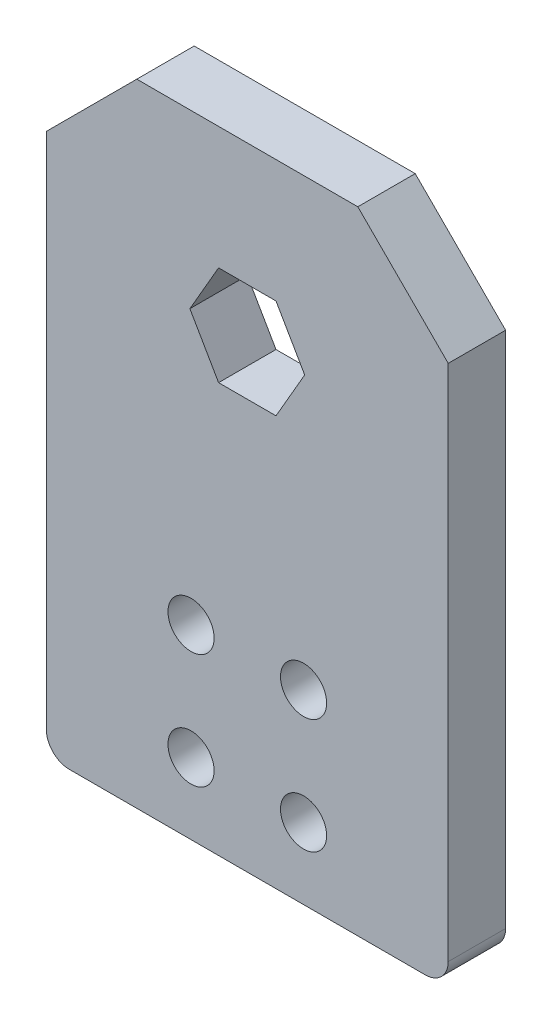
SolidWorks part; units mm, degrees
ref_plane "Front Plane" through (0, 0, 0) normal (0, 0, 1) x (1, 0, 0)
ref_plane "Top Plane" through (0, 0, 0) normal (0, 1, 0) x (1, 0, 0)
ref_plane "Right Plane" through (0, 0, 0) normal (1, 0, 0) x (0, 0, -1)
sketch "Sketch1" plane through (0, 0, 0) normal (0, 0, 1) x (1, 0, 0)
  line L1 (-22.225, -34.925) -> (22.225, -34.925)
  line L2 (-22.225, -34.925) -> (-22.225, 34.925)
  line L3 (-22.225, 34.925) -> (22.225, 34.925)
  line L4 (22.225, -34.925) -> (22.225, 34.925)
  line L5 (-22.225, -34.925) -> (22.225, 34.925) construction
  line L6 (-22.225, 34.925) -> (22.225, -34.925) construction
  point P0 (0, 0)
  dimension "D1" = 44.45
  dimension "D2" = 69.85
extrude "Boss-Extrude1" add sketch "Sketch1" along normal mid plane 6.35
chamfer "Chamfer1" distance 10 angle 45 2 edges at (22.225, 34.925, 0) (-22.225, 34.925, 0)
sketch "Sketch2" plane through (0, 0, 3.175) normal (0, 0, 1) x (1, 0, 0)
  line L1 (12.225, 34.925) -> (-12.225, 34.925) construction
  line L2 (6.35, 15.875) -> (3.175, 21.3743)
  line L3 (3.175, 21.3743) -> (-3.175, 21.3743)
  line L4 (-3.175, 21.3743) -> (-6.35, 15.875)
  line L5 (-6.35, 15.875) -> (-3.175, 10.3757)
  line L6 (-3.175, 10.3757) -> (3.175, 10.3757)
  line L7 (3.175, 10.3757) -> (6.35, 15.875)
  circle A1 centre (0, 15.875) radius 5.4993 construction
  point P12 (0, 0)
  point P13 (0, 12.7)
  dimension "D1" = 19.05
  dimension "D2" = 12.7
extrude "Cut-Extrude1" cut sketch "Sketch2" against normal through all
hole_wizard "Tap Drill for #10-24 Tap1" positions "Sketch4" profile "Sketch5" hole size "#10-24" standard "ANSI Inch"
sketch "Sketch4" plane through (0, -34.925, 0) normal (0, -1, 0) x (-1, 0, 0)
  line L0 (15.875, 0) -> (-15.875, 0) construction
  point P0 (15.875, 0)
  point P2 (-15.875, 0)
  point P13 (0, 0)
  dimension "D1" = 31.75
sketch "Sketch5" plane through (-15.875, -34.925, 0) normal (1, 0, 0) x (0, 0, -1)
  line L0 (0, 0) -> (0, 20.1908)
  line L1 (0, 20.1908) -> (1.8986, 19.05)
  line L2 (1.8986, 19.05) -> (1.8986, 0)
  line L5 (1.8986, 0) -> (0, 0)
  line L10 (0, 20.1908) -> (-1.8987, 19.05) construction
  line L11 (0, -6.35) -> (0, 107.95) construction
  dimension "Hole Dia." = 3.7973
  dimension "Hole Depth" = 19.05
  dimension "Drill Angle" = 118
sketch "Sketch6" plane through (0, 0, 3.175) normal (0, 0, 1) x (1, 0, 0)
  line L0 (-22.225, -34.925) -> (22.225, -34.925) construction
  line L1 (-6.223, -27.051) -> (6.223, -27.051) construction
  line L2 (-6.223, -27.051) -> (-6.223, -14.351) construction
  line L3 (-6.223, -14.351) -> (6.223, -14.351) construction
  line L4 (6.223, -27.051) -> (6.223, -14.351) construction
  line L5 (-6.223, -27.051) -> (6.223, -14.351) construction
  line L6 (-6.223, -14.351) -> (6.223, -27.051) construction
  point P0 (0, -20.701)
  dimension "D1" = 7.874
  dimension "D2" = 12.446
  dimension "D3" = 12.7
hole_wizard "#10 Clearance Hole1" positions "Sketch7" profile "Sketch8" hole size "#10" standard "ANSI Inch"
sketch "Sketch7" plane through (0, 0, 3.175) normal (0, 0, 1) x (1, 0, 0)
  point P0 (-6.223, -14.351)
  point P3 (6.223, -14.351)
  point P6 (6.223, -27.051)
  point P9 (-6.223, -27.051)
sketch "Sketch8" plane through (-6.223, -14.351, 3.175) normal (1, 0, 0) x (0, -1, 0)
  line L0 (0, 0) -> (0, 14.2338)
  line L1 (0, 14.2338) -> (2.5527, 12.7)
  line L2 (2.5527, 12.7) -> (2.5527, 0)
  line L5 (2.5527, 0) -> (0, 0)
  line L10 (0, 14.2338) -> (-2.5527, 12.7) construction
  line L11 (0, -6.35) -> (0, 107.95) construction
  dimension "Hole Dia." = 5.1054
  dimension "Hole Depth" = 12.7
  dimension "Drill Angle" = 118
fillet "Fillet1" radius 2.54 2 edges at (22.225, -34.925, 0) (-22.225, -34.925, 0)
ref_axis "Axis1" through (0, 15.875, 3.175) along (0, 0, 1)
